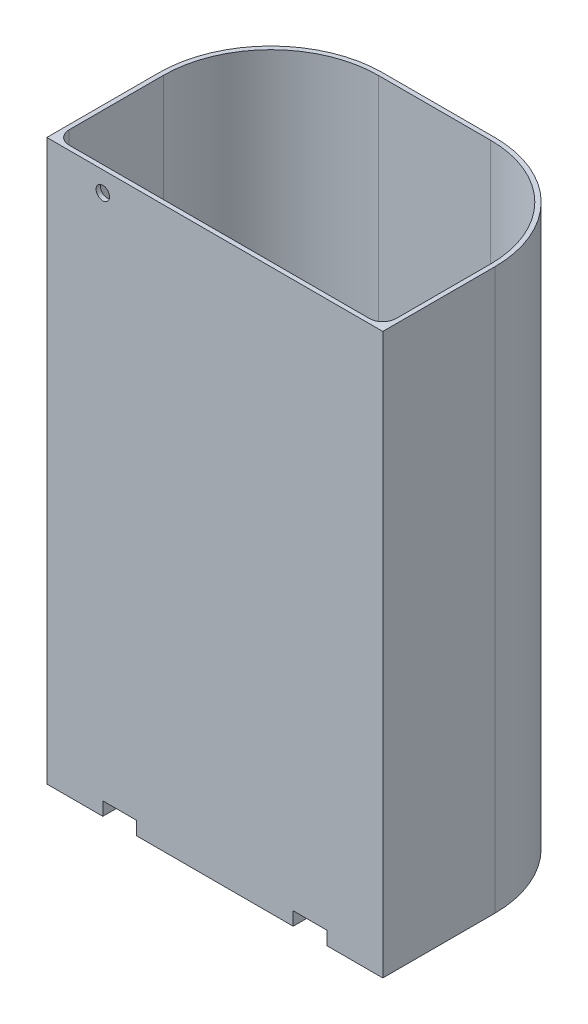
SolidWorks part; units mm, degrees
ref_plane "Front Plane" through (0, 0, 0) normal (0, 0, 1) x (1, 0, 0)
ref_plane "Top Plane" through (0, 0, 0) normal (0, 1, 0) x (1, 0, 0)
ref_plane "Right Plane" through (0, 0, 0) normal (1, 0, 0) x (0, 0, -1)
sketch "Sketch1" plane through (0, 0, 0) normal (0, 1, 0) x (1, 0, 0)
  line L1 (0, 0) -> (150, 0)
  line L2 (0, 0) -> (0, 100)
  line L3 (0, 100) -> (150, 100)
  line L4 (150, 0) -> (150, 100)
  dimension "D1" = 150
  dimension "D2" = 100
extrude "Boss-Extrude1" add sketch "Sketch1" along normal blind 250
fillet "Fillet1" radius 50 2 edges at (0, 125, -100) (150, 125, -100)
sketch "Sketch4" plane through (0, 0, 0) normal (0, -1, 0) x (1, 0, 0)
  line L0 (0, 0) -> (150, 0) construction
  line L1 (25, 0) -> (40, 0)
  line L2 (25, 0) -> (25, -60)
  line L3 (25, -60) -> (40, -60)
  line L4 (40, 0) -> (40, -60)
  line L5 (0, -50) -> (0, 0) construction
  line L6 (125, 0) -> (110, 0)
  line L7 (125, 0) -> (125, -60)
  line L8 (125, -60) -> (110, -60)
  line L9 (110, 0) -> (110, -60)
  line L12 (150, 0) -> (150, -50) construction
  dimension "D1" = 15
  dimension "D2" = 15
  dimension "D3" = 60
  dimension "D4" = 25
  dimension "D5" = 25
extrude "Cut-Extrude2" cut sketch "Sketch4" against normal blind 6
sketch "Sketch5" plane through (0, 6, 0) normal (0, -1, 0) x (1, 0, 0)
  line L0 (40, -60) -> (40, 0) construction
  line L1 (25, -16) -> (40, -16)
  line L2 (25, -16) -> (25, -8)
  line L3 (25, -8) -> (40, -8)
  line L4 (40, -16) -> (40, -8)
  line L5 (125, -60) -> (125, 0) construction
  line L6 (110, -16) -> (125, -16)
  line L7 (110, -16) -> (110, -8)
  line L8 (110, -8) -> (125, -8)
  line L9 (125, -16) -> (125, -8)
  line L10 (125, 0) -> (110, 0) construction
  line L11 (40, 0) -> (25, 0) construction
  line L12 (110, 0) -> (110, -60) construction
  line L13 (25, 0) -> (25, -60) construction
  dimension "D1" = 8
  dimension "D2" = 8
  dimension "D3" = 8
  dimension "D4" = 8
extrude "Cut-Extrude3" cut sketch "Sketch5" against normal blind 4
chamfer "Chamfer2" distance 2 angle 60 4 edges at (117.5, 6, -8) (117.5, 6, -16) (32.5, 6, -8) (32.5, 6, -16) first distance on face at (117.5, 6, -4) first distance on face at (117.5, 6, -38) first distance on face at (32.5, 6, -4) first distance on face at (32.5, 6, -38)
shell "Shell1" thickness 2 removed face at (75, 250, -53.4518)
fillet "Fillet4" radius 6 16 edges at (12.5, 2, -2) (2, 2, -26) (16.0589, 2, -83.9411) (75, 2, -98) (133.9411, 2, -83.9411) (148, 2, -26) (137.5, 2, -2) (127, 2, -32) (117.5, 2, -62) (108, 2, -32) (75, 2, -2) (42, 2, -32) (32.5, 2, -62) (23, 2, -32) (2, 126, -2) (148, 126, -2)
sketch "Sketch6" plane through (0, 2, 0) normal (0, 1, 0) x (1, 0, 0)
  line L0 (67, 81.0752) -> (77, 81.0752)
  line L1 (42, 62) -> (42, 19.1547) construction
  line L2 (102, 8) -> (102, 68) construction
  dimension "D1" = 10
  dimension "D2" = 25
  dimension "D3" = 25
extrude "Extrude-Thin1" add sketch "Sketch6" along normal blind 9.5 thin thin type mid plane wall 3
fillet "Fillet5" radius 3 4 edges at (72, 2, -82.5752) (77, 2, -81.0752) (72, 2, -79.5752) (67, 2, -81.0752)
sketch "Sketch7" plane through (0, 0, -79.5752) normal (0, 0, 1) x (1, 0, 0)
  line L0 (67, 11.5) -> (67, 5) construction
  line L1 (67, 5) -> (77, 5) construction
  circle A0 centre (72, 9) radius 3
  dimension "D1" = 6
  dimension "D2" = 5
  dimension "D3" = 4
extrude "Cut-Extrude4" cut sketch "Sketch7" against normal up to next
fillet "Fillet6" radius 0.5 2 edges at (73.6583, 11.5, -81.0752) (70.3417, 11.5, -81.0752)
sketch "Sketch8" plane through (0, 0, -2) normal (0, 0, -1) x (-1, 0, 0)
  line L0 (-2, 250) -> (-2, 8) construction
  line L1 (-8, 250) -> (-142, 250) construction
  circle A0 centre (-25, 241) radius 3
  dimension "D1" = 23
  dimension "D2" = 9
  dimension "D3" = 6
extrude "Cut-Extrude5" cut sketch "Sketch8" against normal blind 10
